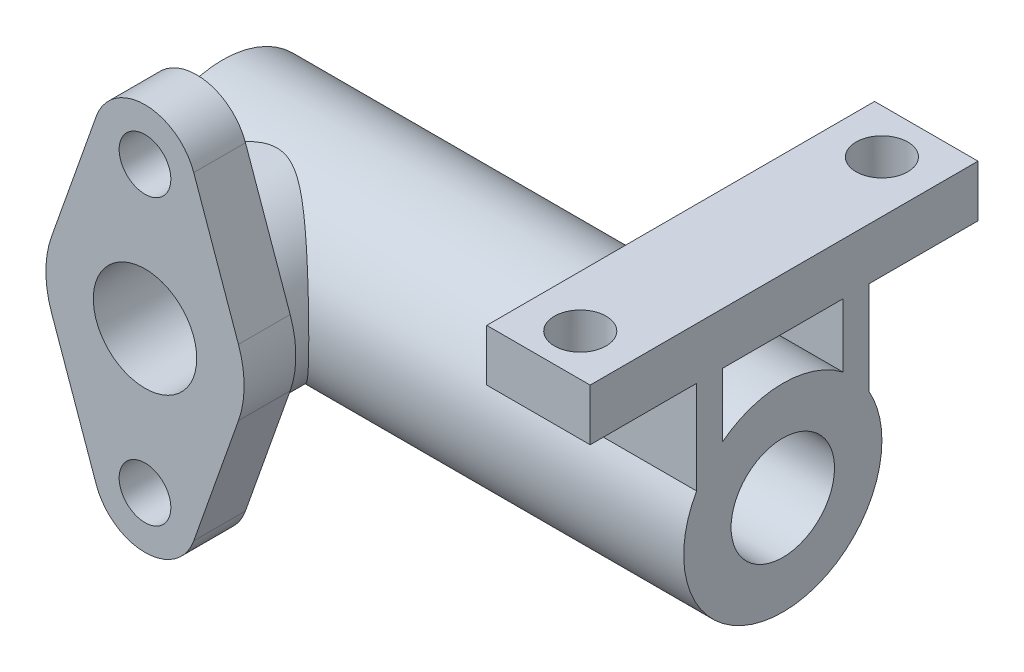
SolidWorks part; units mm, degrees
ref_plane "前视基准面" through (0, 0, 0) normal (0, 0, 1) x (1, 0, 0)
ref_plane "上视基准面" through (0, 0, 0) normal (0, 1, 0) x (1, 0, 0)
ref_plane "右视基准面" through (0, 0, 0) normal (1, 0, 0) x (0, 0, -1)
sketch "草图1" plane through (0, 0, 0) normal (1, 0, 0) x (0, 0, -1)
  circle A0 centre (0, 0) radius 23
extrude "凸台-拉伸1" add sketch "草图1" along normal blind 65 and the other way blind 65
ref_plane "基准面1" through (65, 0, 0) normal (1, 0, 0) x (0, 0, -1)
sketch "草图4" plane through (65, 0, 0) normal (1, 0, 0) x (0, 0, -1)
  line L0 (-20, 11.3578) -> (-14, 18.2483)
  line L1 (-20, 0) -> (20, 0)
  line L2 (-20, 0) -> (-20, 33)
  line L3 (-20, 45) -> (20, 45)
  line L4 (20, 0) -> (20, 33)
  line L9 (-44.7036, 33) -> (45.2964, 33)
  line L10 (-44.7036, 33) -> (-44.7036, 45)
  line L11 (-44.7036, 45) -> (45.2964, 45)
  line L12 (45.2964, 33) -> (45.2964, 45)
  line L14 (-14, 18.2483) -> (-14, 33)
  line L15 (-14, 33) -> (14, 33)
  line L16 (14, 18.2483) -> (14, 33)
  line L17 (-1.6475, 22.9409) -> (0, 24) construction
  line L18 (0, 24) -> (1.6475, 22.9409) construction
  line L19 (14, 18.2483) -> (20, 11.3578)
  arc A1 (14, 18.2483) -> (-14, 18.2483) centre (0, 0) ccw
  circle A2 centre (0, 0) radius 23 construction
  point P4 (0, 39)
  point P9 (0, 24)
  dimension "D1" = 12
extrude "凸台-拉伸3" add sketch "草图4" against normal blind 24 contours L9 L12 L11 L3 L10 | L0 L14 L9 L2 | L16 L19 L4 L9 region at (65, 23.7928, 17.1893) region at (65, 39, -0.2964) region at (65, 23.7928, -17.1893)
ref_plane "基准面7" through (0, 45, 0) normal (0, 1, 0) x (1, 0, 0)
sketch "草图7" plane through (0, 45, 0) normal (0, 1, 0) x (1, 0, 0)
  circle A0 centre (53, 35) radius 6
  circle A1 centre (53, -35) radius 6
extrude "切除-拉伸3" cut sketch "草图7" against normal blind 24
sketch "草图8" plane through (0, 0, 0) normal (0, 0, 1) x (1, 0, 0)
  circle A0 centre (-43, 0) radius 21
extrude "凸台-拉伸4" add sketch "草图8" along normal blind 40
sketch "草图3" plane through (0, 0, 0) normal (1, 0, 0) x (0, 0, -1)
  circle A0 centre (0, 0) radius 12
extrude "切除-拉伸2" cut sketch "草图3" against normal blind 65 and the other way blind 65
sketch "草图2" plane through (0, 0, 0) normal (1, 0, 0) x (0, 0, -1)
  circle A0 centre (0, 0) radius 15
extrude "切除-拉伸1" cut sketch "草图2" against normal blind 47 and the other way blind 47
ref_plane "基准面8" through (0, 0, 40) normal (0, 0, 1) x (1, 0, 0)
sketch "草图10" plane through (0, 0, 40) normal (0, 0, 1) x (1, 0, 0)
  line L0 (-54.3137, 37) -> (-64.6846, 7.6667)
  line L1 (-31.6863, 37) -> (-21.3154, 7.6667)
  line L2 (-54.3137, -37) -> (-64.6846, -7.6667)
  line L3 (-31.6863, -37) -> (-21.3154, -7.6667)
  arc A0 (-64.6846, 7.6667) -> (-64.6846, -7.6667) centre (-43, 0) ccw
  arc A1 (-31.6863, 37) -> (-54.3137, 37) centre (-43, 33) ccw
  arc A2 (-54.3137, -37) -> (-31.6863, -37) centre (-43, -33) ccw
  arc A3 (-21.3154, -7.6667) -> (-21.3154, 7.6667) centre (-43, 0) ccw
extrude "凸台-拉伸5" add sketch "草图10" against normal blind 12
sketch "草图11" plane through (0, 0, 40) normal (0, 0, 1) x (1, 0, 0)
  circle A0 centre (-43, 0) radius 12
  circle A1 centre (-43, 33) radius 6
  circle A2 centre (-43, -33) radius 6
extrude "切除-拉伸4" cut sketch "草图11" against normal blind 40
